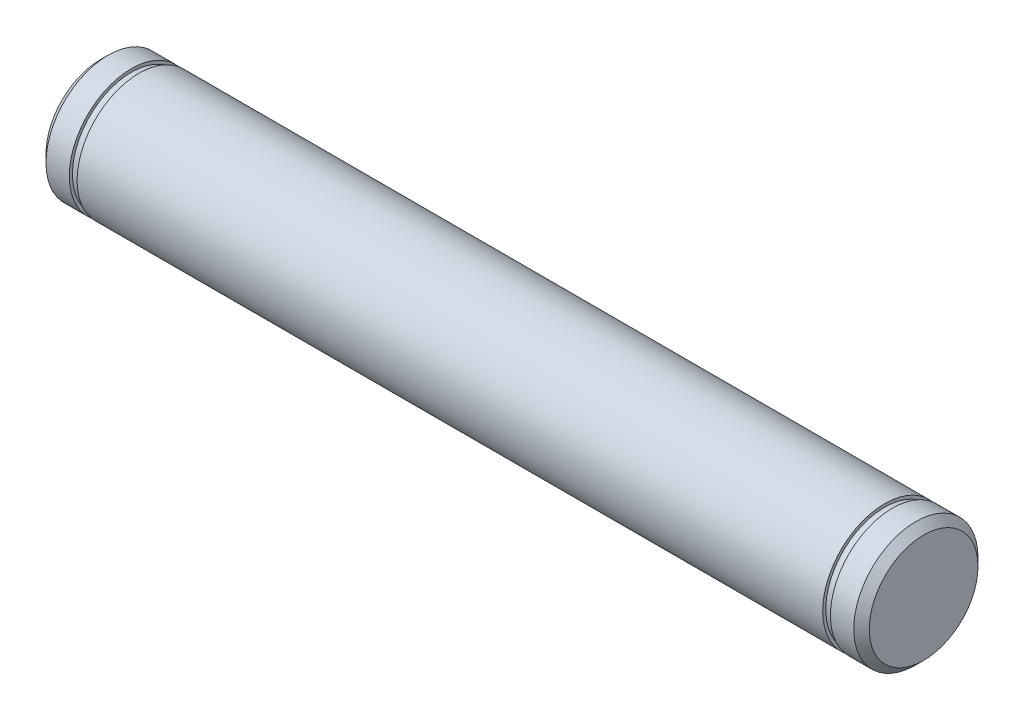
SolidWorks part; units mm, degrees
ref_plane "Front" through (0, 0, 0) normal (0, 0, 1) x (1, 0, 0)
ref_plane "Top" through (0, 0, 0) normal (0, 1, 0) x (1, 0, 0)
ref_plane "Right" through (0, 0, 0) normal (1, 0, 0) x (0, 0, -1)
sketch "Sketch1" plane through (0, 0, 0) normal (1, 0, 0) x (0, 0, -1)
  circle A0 centre (0, 0) radius 2
  dimension "D1" = 4
extrude "Boss-Extrude1" add sketch "Sketch1" along normal blind 26.5
sketch "Sketch2" plane through (26.5, 0, 0) normal (1, 0, 0) x (0, 0, -1)
  circle A0 centre (0, 0) radius 1.9
  circle A1 centre (0, 0) radius 2.4981
  dimension "D1" = 3.8
extrude "Cut-Extrude2" cut sketch "Sketch2" against normal blind 0.25 from offset 1 offset against normal yes
sketch "Sketch3" plane through (0, 0, 0) normal (-1, 0, 0) x (0, 0, 1)
  circle A0 centre (0, 0) radius 1.9
  circle A1 centre (0, 0) radius 2.5
extrude "Cut-Extrude3" cut sketch "Sketch3" against normal blind 0.25 from offset 1 offset against normal yes
chamfer "Chamfer1" distance 0.25 angle 45 2 edges at (0, 0, -2) (26.5, 0, -2)
